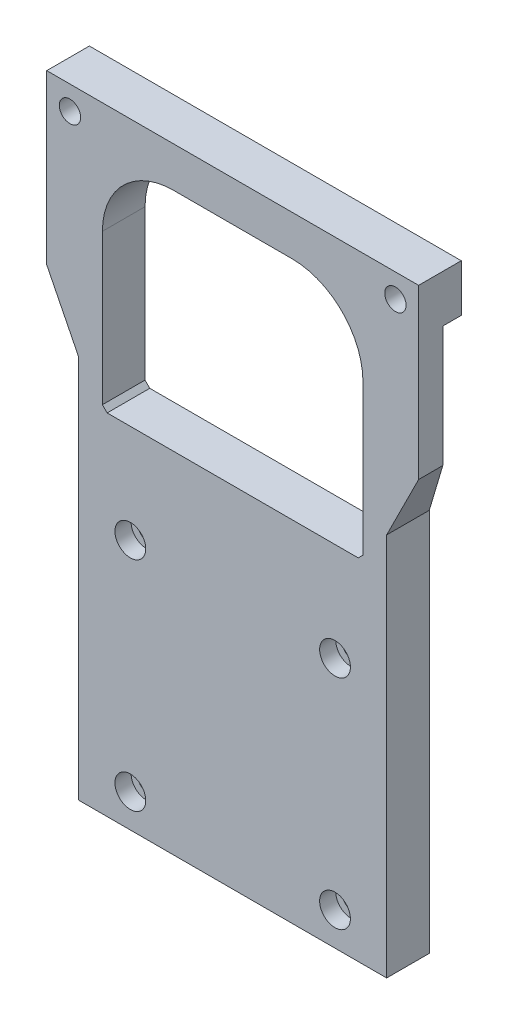
SolidWorks part; units mm, degrees
ref_plane "Top" through (0, 0, 0) normal (0, 0, 1) x (1, 0, 0)
ref_plane "Front" through (0, 0, 0) normal (0, 1, 0) x (1, 0, 0)
ref_plane "Right" through (0, 0, 0) normal (1, 0, 0) x (0, 0, -1)
sketch "Sketch1" plane through (0, 0, 0) normal (0, 0, 1) x (1, 0, 0)
  line L1 (0, 0) -> (65, 0)
  line L2 (0, 0) -> (0, 130)
  line L3 (0, 130) -> (65, 130)
  line L4 (65, 0) -> (65, 130)
  dimension "D1" = 65
  dimension "D2" = 130
extrude "Boss-Extrude1" add sketch "Sketch1" along normal blind 9
sketch "Sketch2" plane through (0, 0, 9) normal (0, 0, 1) x (1, 0, 0)
  line L0 (65, 130) -> (0, 130) construction
  line L1 (-6.75, 130) -> (71.75, 130)
  line L2 (-6.75, 130) -> (-6.75, 94.5)
  line L3 (-6.75, 94.5) -> (71.75, 94.5)
  line L4 (71.75, 130) -> (71.75, 94.5)
  line L5 (0, 130) -> (0, 0) construction
  dimension "D1" = 78.5
  dimension "D2" = 6.75
  dimension "D3" = 35.5
extrude "Boss-Extrude2" add sketch "Sketch2" against normal blind 9
sketch "Sketch3" plane through (0, 130, 0) normal (0, 1, 0) x (1, 0, 0)
  line L0 (0, 0) -> (-6.75, -3.8971)
  line L1 (71.75, 0) -> (-6.75, 0) construction
  line L2 (-6.75, -3.8971) -> (-9.75, -3.8971)
  line L3 (-9.75, -3.8971) -> (-9.75, 6.1029)
  line L4 (-9.75, 6.1029) -> (75.25, 6.1029)
  line L5 (75.25, 6.1029) -> (75.25, -3.8971)
  line L6 (75.25, -3.8971) -> (71.75, -3.8971)
  line L7 (71.75, 0) -> (71.75, -9) construction
  line L8 (71.75, -3.8971) -> (65, 0)
  line L9 (65, 0) -> (0, 0)
  line L11 (-6.75, 0) -> (-6.75, -9) construction
  point P11 (0, 0)
  point P13 (0, 0)
  dimension "D1" = 150
  dimension "D2" = 150
  dimension "D3" = 65
  dimension "D4" = 10
  dimension "D5" = 85
  dimension "D6" = 3
extrude "Cut-Extrude1" cut sketch "Sketch3" against normal through all from offset 10 offset against normal yes
sketch "Sketch4" plane through (0, 0, 9) normal (0, 0, 1) x (1, 0, 0)
  line L0 (-1.85, 125) -> (66.85, 125)
  line L1 (-6.75, 130) -> (-6.75, 94.5) construction
  line L5 (71.75, 130) -> (-6.75, 130) construction
  point P2 (32.5, 125)
  dimension "D1" = 68.7
  dimension "D2" = 39.25
  dimension "D3" = 5
hole_wizard "M4 Clearance Hole1" positions "Sketch5" profile "Sketch6" hole size "M4" standard "DIN" end condition through all
sketch "Sketch5" plane through (0, 0, 9) normal (0, 0, 1) x (1, 0, 0)
  point P0 (-1.85, 125)
  point P3 (66.85, 125)
sketch "Sketch6" plane through (-1.85, 125, 9) normal (1, 0, 0) x (0, -1, 0)
  line L0 (0, 0) -> (0, 9)
  line L1 (0, 9) -> (2.25, 9)
  line L2 (2.25, 9) -> (2.25, 0)
  line L5 (2.25, 0) -> (0, 0)
  line L11 (0, -6.35) -> (0, 107.95) construction
  dimension "Thru Hole Dia." = 4.5
  dimension "Thru Hole Depth" = 9
sketch "Sketch7" plane through (0, 0, 9) normal (0, 0, 1) x (1, 0, 0)
  line L0 (71.75, 130) -> (-6.75, 130) construction
  line L1 (10.9, 53) -> (54.1, 53)
  line L2 (10.9, 53) -> (10.9, 7)
  line L3 (10.9, 7) -> (54.1, 7)
  line L4 (54.1, 53) -> (54.1, 7)
  line L5 (0, 94.5) -> (0, 0) construction
  dimension "D1" = 77
  dimension "D2" = 43.2
  dimension "D3" = 46
  dimension "D4" = 10.9
hole_wizard "CBORE for M3 Hex Socket Head Cap Screw1" positions "Sketch9" profile "Sketch10" counterbore size "M3" standard "DIN" end condition through all
sketch "Sketch9" plane through (0, 0, 9) normal (0, 0, 1) x (1, 0, 0)
  point P0 (10.9, 53)
  point P3 (54.1, 53)
  point P6 (54.1, 7)
  point P9 (10.9, 7)
sketch "Sketch10" plane through (10.9, 53, 9) normal (1, 0, 0) x (0, -1, 0)
  line L0 (0, 0) -> (0, 9)
  line L1 (0, 9) -> (1.7, 9)
  line L3 (1.7, 9) -> (1.7, 3.4)
  line L4 (1.7, 3.4) -> (3.25, 3.4)
  line L5 (3.25, 3.4) -> (3.25, 0)
  line L7 (3.25, 0) -> (0, 0)
  line L11 (0, -6.35) -> (0, 107.95) construction
  dimension "Thru Hole Dia." = 3.4
  dimension "Thru Hole Depth" = 9
  dimension "C'Bore Dia." = 6.5
  dimension "C'Bore Depth" = 3.4
sketch "Sketch11" plane through (0, 0, 0) normal (0, 0, -1) x (-1, 0, 0)
  line L0 (-71.75, 130) -> (6.75, 130) construction
  line L1 (-62.6353, 125) -> (-64.7427, 128.65)
  line L2 (-64.7427, 128.65) -> (-68.9573, 128.65)
  line L3 (-68.9573, 128.65) -> (-71.0647, 125)
  line L4 (-71.0647, 125) -> (-68.9573, 121.35)
  line L5 (-68.9573, 121.35) -> (-64.7427, 121.35)
  line L6 (-64.7427, 121.35) -> (-62.6353, 125)
  line L7 (-2.3647, 125) -> (-0.2573, 121.35)
  line L8 (-0.2573, 121.35) -> (3.9573, 121.35)
  line L9 (3.9573, 121.35) -> (6.0647, 125)
  line L10 (6.0647, 125) -> (3.9573, 128.65)
  line L11 (3.9573, 128.65) -> (-0.2573, 128.65)
  line L12 (-0.2573, 128.65) -> (-2.3647, 125)
  circle A0 centre (-66.85, 125) radius 3.65 construction
  circle A1 centre (1.85, 125) radius 3.65 construction
  dimension "D1" = 7.3
  dimension "D2" = 7.3
extrude "Cut-Extrude3" cut sketch "Sketch11" against normal blind 3.5
sketch "Sketch12" plane through (0, 0, 9) normal (0, 0, 1) x (1, 0, 0)
  line L0 (0, 94.5) -> (0, 0) construction
  line L1 (5, 121.5) -> (60, 121.5)
  line L2 (5, 121.5) -> (5, 73.8)
  line L3 (5, 73.8) -> (60, 73.8)
  line L4 (60, 121.5) -> (60, 73.8)
  line L5 (71.75, 130) -> (-6.75, 130) construction
  circle A0 centre (10.9, 53) radius 3.25 construction
  dimension "D1" = 55
  dimension "D2" = 5
  dimension "D3" = 8.5
  dimension "D4" = 20.8
extrude "Cut-Extrude4" cut sketch "Sketch12" against normal blind 9
chamfer "Chamfer1" distance 6.75 distance2 13.5 2 edges at (65, 94.5, 4.5) (0, 94.5, 4.5) first distance on face at (68.375, 94.5, 5.4743) first distance on face at (-3.375, 94.5, 5.4743)
fillet "Fillet1" radius 15 2 edges at (60, 121.5, 4.5) (5, 121.5, 4.5)
chamfer "Chamfer2" distance 1 angle 45 2 edges at (5, 73.8, 4.5) (60, 73.8, 4.5)
